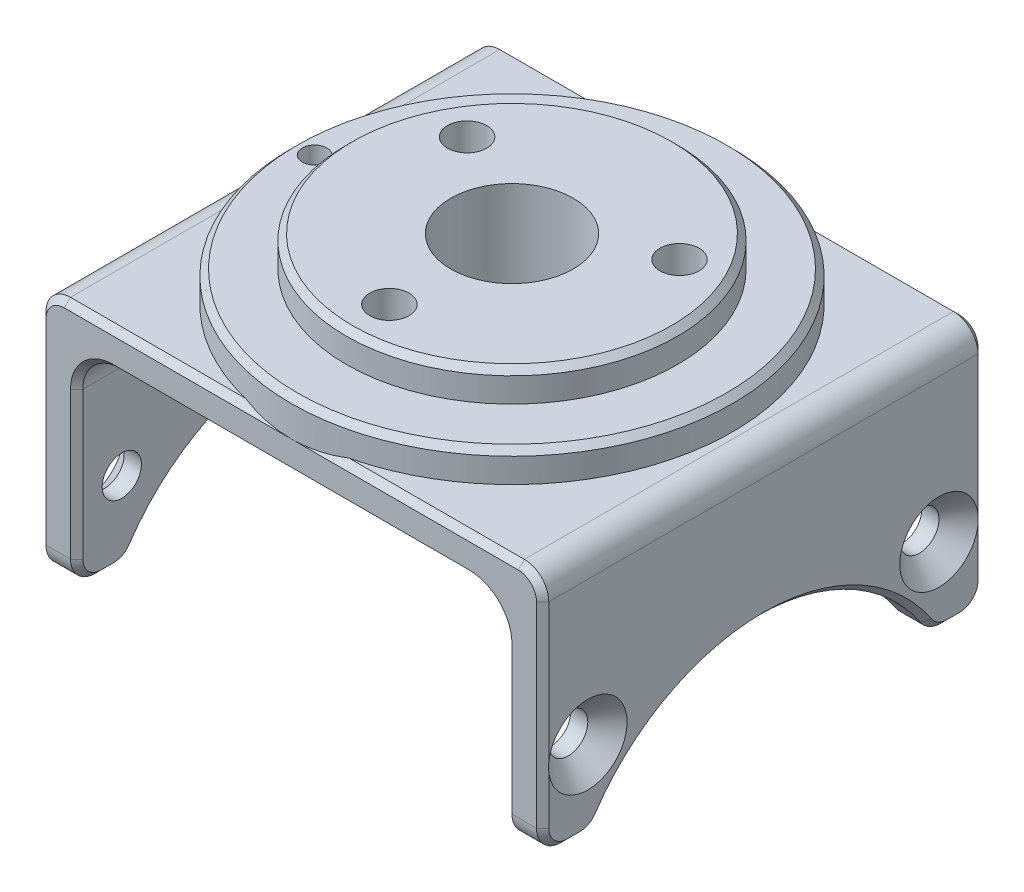
SolidWorks part; units mm, degrees
material "6061 合金"
ref_plane "前视基准面" through (0, 0, 0) normal (0, 0, 1) x (1, 0, 0)
ref_plane "上视基准面" through (0, 0, 0) normal (0, 1, 0) x (1, 0, 0)
ref_plane "右视基准面" through (0, 0, 0) normal (1, 0, 0) x (0, 0, -1)
other "Configuration Table"
sketch "草图1" plane through (0, 0, 0) normal (0, 0, 1) x (1, 0, 0)
  point P3 (0, 0)
  point P9 (0, 0)
sketch "草图2" plane through (0, 0, 0) normal (0, 0, 1) x (1, 0, 0)
  line L0 (0, 0) -> (29.4331, 0) construction
  line L1 (0, 0) -> (0, 29.9014) construction
  line L2 (17.5, 17) -> (17.5, 0)
  line L3 (20.5, 0) -> (20.5, 20)
  line L4 (-20.5, 0) -> (-20.5, 20)
  line L5 (-17.5, 17) -> (-17.5, 0)
  line L6 (-20.5, 20) -> (20.5, 20)
  line L7 (-17.5, 17) -> (17.5, 17)
  line L8 (-20.5, 0) -> (-17.5, 0)
  line L9 (17.5, 0) -> (20.5, 0)
  dimension "D1" = 3
  dimension "D2" = 41
  dimension "D3" = 3
  dimension "D4" = 20
extrude "凸台-拉伸1" add sketch "草图2" along normal mid plane 36
sketch "草图3" plane through (20.5, 0, 0) normal (1, 0, 0) x (0, 0, -1)
  line L0 (0, 0) -> (-23.178, 0) construction
  line L1 (0, 0) -> (0, 16.1566) construction
  line L2 (-18, 20) -> (18, 20) construction
  circle A1 centre (0, -8) radius 16
  dimension "D1" = 28
  dimension "D2" = 32
extrude "切除-拉伸1" cut sketch "草图3" against normal blind 46
sketch "草图4" plane through (20.5, 0, 0) normal (1, 0, 0) x (0, 0, -1)
  line L0 (0, -8) -> (20.25, -8) construction
  line L1 (0, -8) -> (14.3189, 6.3189) construction
  line L2 (0, -8) -> (0, 20) construction
  line L3 (-18, 20) -> (18, 20) construction
  circle A0 centre (0, -8) radius 20.25 construction
  arc A1 (13.8564, 0) -> (-13.8564, 0) centre (0, -8) ccw construction
  circle A2 centre (14.3189, 6.3189) radius 1.5
  circle A3 centre (-14.3189, 6.3189) radius 1.5
  point P7 (14.3189, 6.3189)
  point P8 (-14.3189, 6.3189)
  point P18 (14.3189, 6.3189)
  dimension "D1" = 40.5
  dimension "D3" = 3
  dimension "D2" = 45
sketch "草图11" plane through (0, 20, 0) normal (0, 1, 0) x (1, 0, 0)
  circle A0 centre (0, 0) radius 13.5
  dimension "D1" = 27
extrude "凸台-拉伸2" add sketch "草图11" along normal blind 5
sketch "草图12" plane through (0, 20, 0) normal (0, 1, 0) x (1, 0, 0)
  circle A1 centre (0, 0) radius 18
  dimension "D1" = 36
extrude "凸台-拉伸5" add sketch "草图12" along normal blind 2.5
sketch "草图13" plane through (0, 22.5, 0) normal (0, 1, 0) x (1, 0, 0)
  circle A0 centre (0, 0) radius 16.1 construction
  circle A1 centre (-16.1, 0) radius 1
  point P3 (-16.1, 0)
  dimension "D1" = 32.2
  dimension "D2" = 2
sketch "草图7" plane through (0, 17, 0) normal (0, -1, 0) x (1, 0, 0)
  line L0 (0, 0) -> (0, 10) construction
  circle A0 centre (0, 0) radius 10 construction
  circle A1 centre (0, 10) radius 1.5
  circle A2 centre (8.6603, -5) radius 1.5
  circle A3 centre (-8.6603, -5) radius 1.5
  point P4 (0, 10)
  point P9 (8.6603, -5)
  point P11 (-8.6603, -5)
  point P19 (0, 10)
  dimension "D1" = 20
  dimension "D2" = 3
  dimension "D3" = 3
hole_wizard "M3 开槽半沉头螺钉的锥形沉头孔3" positions "草图7" profile "草图8" countersink size "M3" standard "GB" end condition up to next
sketch "草图8" plane through (0, 17, 10) normal (1, 0, 0) x (0, 0, -1)
  line L0 (0, 0) -> (0, 8)
  line L1 (0, 8) -> (1.6, 8)
  line L2 (1.6, 8) -> (1.6, 1.6)
  line L3 (1.6, 1.6) -> (3.2, 0)
  line L5 (3.2, 0) -> (0, 0)
  line L6 (-1.6, 1.6) -> (-3.2, 0) construction
  line L11 (0, -6.35) -> (0, 107.95) construction
  dimension "通孔孔直径" = 3.2
  dimension "通孔孔深度" = 8
  dimension "近端锥形沉头孔直径" = 6.4
  dimension "近端锥形沉头孔角度" = 90
sketch "草图9" plane through (0, 17, 0) normal (0, -1, 0) x (1, 0, 0)
  circle A0 centre (0, 0) radius 5
  dimension "D1" = 10
extrude "切除-拉伸2" cut sketch "草图9" against normal blind 46
hole_wizard "Ø2.0mm 暗销孔1" positions "草图13" profile "草图14" hole size "Ø2.0" standard "GB"
sketch "草图14" plane through (-16.1, 22.5, 0) normal (1, 0, 0) x (0, 0, 1)
  line L0 (0, 0) -> (0, 4.8009)
  line L1 (0, 4.8009) -> (1, 4.2)
  line L2 (1, 4.2) -> (1, 0)
  line L5 (1, 0) -> (0, 0)
  line L10 (0, 4.8009) -> (-1, 4.2) construction
  line L11 (0, -6.35) -> (0, 107.95) construction
  dimension "孔直径" = 2
  dimension "孔深度" = 4.2
  dimension "导头角度" = 118
hole_wizard "M3 开槽半沉头螺钉的锥形沉头孔1" positions "草图4" profile "草图18" countersink size "M3" standard "GB"
sketch "草图18" plane through (20.5, 6.3189, -14.3189) normal (0, 1, 0) x (0, 0, -1)
  line L0 (0, 0) -> (0, 6.9614)
  line L1 (0, 6.9614) -> (1.6, 6)
  line L2 (1.6, 6) -> (1.6, 1.6)
  line L3 (1.6, 1.6) -> (3.2, 0)
  line L5 (3.2, 0) -> (0, 0)
  line L6 (-1.6, 1.6) -> (-3.2, 0) construction
  line L10 (0, 6.9614) -> (-1.6, 6) construction
  line L11 (0, -6.35) -> (0, 107.95) construction
  dimension "孔直径" = 3.2
  dimension "孔深度" = 6
  dimension "近端锥形沉头孔直径" = 6.4
  dimension "近端锥形沉头孔角度" = 90
  dimension "导头角度" = 118
sketch "草图19" plane through (-20.5, 0, 0) normal (-1, 0, 0) x (0, 0, 1)
  circle A0 centre (-14.3189, 6.3189) radius 1.5
  circle A1 centre (14.3189, 6.3189) radius 1.5
  point P0 (-14.3189, 6.3189)
  point P3 (14.3189, 6.3189)
hole_wizard "M3 开槽半沉头螺钉的锥形沉头孔2" positions "草图19" profile "草图20" countersink size "M3" standard "GB"
sketch "草图20" plane through (-20.5, 6.3189, -14.3189) normal (0, 1, 0) x (0, 0, 1)
  line L0 (0, 0) -> (0, 6.9614)
  line L1 (0, 6.9614) -> (1.6, 6)
  line L2 (1.6, 6) -> (1.6, 1.6)
  line L3 (1.6, 1.6) -> (3.2, 0)
  line L5 (3.2, 0) -> (0, 0)
  line L6 (-1.6, 1.6) -> (-3.2, 0) construction
  line L10 (0, 6.9614) -> (-1.6, 6) construction
  line L11 (0, -6.35) -> (0, 107.95) construction
  dimension "孔直径" = 3.2
  dimension "孔深度" = 6
  dimension "近端锥形沉头孔直径" = 6.4
  dimension "近端锥形沉头孔角度" = 90
  dimension "导头角度" = 118
fillet "圆角1" radius 2 8 edges at (19, 0, -18) (19, 0, -13.8564) (19, 0, 13.8564) (19, 0, 18) (-19, 0, -18) (-19, 0, -13.8564) (-19, 0, 13.8564) (-19, 0, 18)
fillet "圆角2" radius 3 2 edges at (-17.5, 17, 0) (17.5, 17, 0)
fillet "圆角3" radius 2 2 edges at (-20.5, 20, 0) (20.5, 20, 0)
chamfer "倒角3" distance 0.5 angle 45 52 edges at (20.5, 8, 0) (20.5, 0.2362, -14.0238) (20.5, 0.2362, 14.0238) (20.5, 0, -15.4833) (20.5, 0, 15.4833) (20.5, 0.5858, -17.4142) (20.5, 0.5858, 17.4142) (20.5, 10, -18) (20.5, 10, 18) (19.9142, 19.4142, -18) (19.9142, 19.4142, 18) (9.25, 20, -18) (9.25, 20, 18) (-9.25, 20, -18) (-9.25, 20, 18) (-19.9142, 19.4142, -18) (-19.9142, 19.4142, 18) (-20.5, 10, -18) (-20.5, 10, 18) (-20.5, 0.5858, -17.4142) (-20.5, 0.5858, 17.4142) (-20.5, 0, -15.4833) (-20.5, 0, 15.4833) (-20.5, 0.2362, -14.0238) (-20.5, 0.2362, 14.0238) (-20.5, 8, 0) (0, 17, -18) (-16.6213, 16.1213, -18) (16.6213, 16.1213, -18) (-17.5, 8, -18) (17.5, 8, -18) (-17.5, 0.5858, -17.4142) (17.5, 0.5858, -17.4142) (-17.5, 0, -15.4833) (17.5, 0, -15.4833) (-17.5, 0.2362, -14.0238) (17.5, 0.2362, -14.0238) (-17.5, 8, 0) (17.5, 8, 0) (-17.5, 0.2362, 14.0238) (17.5, 0.2362, 14.0238) (-17.5, 0, 15.4833) (17.5, 0, 15.4833) (-17.5, 0.5858, 17.4142) (17.5, 0.5858, 17.4142) (-17.5, 8, 18) (17.5, 8, 18) (-16.6213, 16.1213, 18) (16.6213, 16.1213, 18) (0, 17, 18) (0, 25, 13.5) (0, 22.5, 18)
